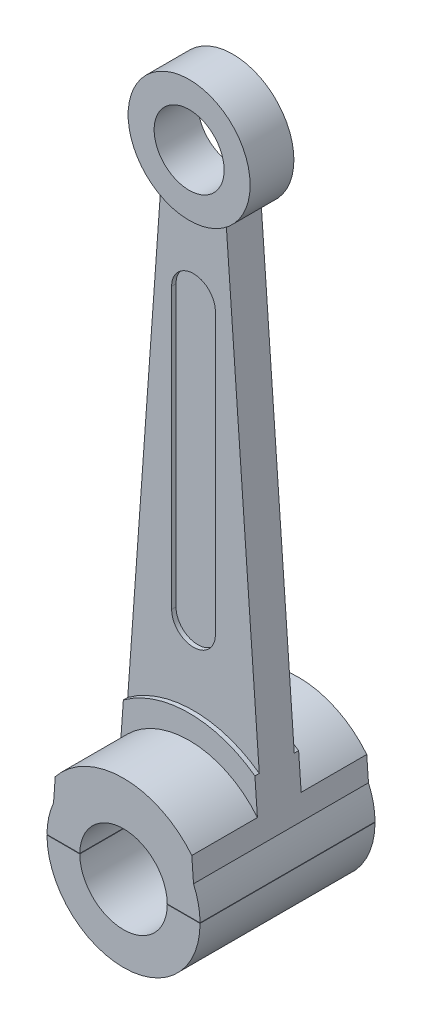
SolidWorks part; units mm, degrees
ref_plane "Front Plane" through (0, 0, 0) normal (0, 0, 1) x (1, 0, 0)
ref_plane "Top Plane" through (0, 0, 0) normal (0, 1, 0) x (1, 0, 0)
ref_plane "Right Plane" through (0, 0, 0) normal (1, 0, 0) x (0, 0, -1)
sketch "Sketch2" plane through (0, 0, 0) normal (0, 0, 1) x (1, 0, 0)
  line L0 (-2.989, 6.37) -> (-3.889, -4.2127)
  line L1 (-2.239, 7.5462) -> (-2.239, -6.1438) construction
  line L2 (-1.489, 6.37) -> (-0.589, -4.2127)
  line L3 (-2.739, 4.5462) -> (-2.739, -1.8525)
  line L4 (-1.739, 4.5462) -> (-1.739, -1.8525)
  circle A0 centre (-2.239, 7.5462) radius 1.395
  circle A1 centre (-2.239, 7.5462) radius 0.8
  circle A2 centre (-2.239, -6.1438) radius 2.54
  circle A3 centre (-2.239, -6.1438) radius 1
  arc A4 (-1.739, 4.5462) -> (-2.739, 4.5462) centre (-2.239, 4.5462) ccw
  arc A5 (-2.739, -1.8525) -> (-1.739, -1.8525) centre (-2.239, -1.8525) ccw
  dimension "D1" = 5.08
  dimension "D2" = 2
  dimension "D3" = 2.79
  dimension "D4" = 1.6
  dimension "D5" = 13.69
  dimension "D6" = 1
  dimension "D7" = 1
  dimension "D8" = 1.5
  dimension "D9" = 3
  dimension "D10" = 3.3
extrude "Boss-Extrude1" add sketch "Sketch2" along normal mid plane 1 contours A1 A0 | A2 A3 region at (-2.8907, 8.7348, 0) region at (-2.239, -3.6757, 0)
extrude "Boss-Extrude2" add sketch "Sketch2<4>" along normal mid plane 0.8 contours L1 A0 L0 A2 A5 L3 A4 | A0 L1 A4 L4 A5 A2 L2 region at (-3.0368, 0.2996, 0) region at (-1.4411, 0.2996, 0)
sketch "Sketch2<4>" plane through (0, 0, 0) normal (0, 0, 1) x (1, 0, 0) same geometry as "Sketch2"
extrude "Boss-Extrude3" add sketch "Sketch2<5>" along normal mid plane 0.6 contours L1 A4 L3 A5 | A4 L1 A5 L4 region at (-1.9931, 1.3469, 0) region at (-2.4848, 1.3469, 0)
sketch "Sketch2<5>" plane through (0, 0, 0) normal (0, 0, 1) x (1, 0, 0) same geometry as "Sketch2"
sketch "Sketch3" plane through (0, 0, 0.5) normal (0, 0, 1) x (1, 0, 0)
  circle A0 centre (-2.239, -6.1438) radius 1
  circle A1 centre (-2.239, -6.1438) radius 2
  dimension "D1" = 4
  dimension "D2" = 2
extrude "Boss-Extrude4" add sketch "Sketch3" along normal blind 1.5 and the other way blind 2.5
sketch "Sketch4" plane through (0, 0, 2) normal (0, 0, 1) x (1, 0, 0)
  line L0 (-5.2042, -4.2844) -> (-2.989, 6.37)
  line L1 (-1.489, 6.37) -> (0.7263, -4.2844)
  line L2 (-1.489, 6.37) -> (-0.589, -4.2127) construction
  line L3 (-3.839, -5.4349) -> (-2.989, 6.37)
  line L4 (-0.639, -5.4349) -> (-1.489, 6.37)
  arc A0 (-3.839, -5.4349) -> (-0.639, -5.4349) centre (-2.239, -6.1438) ccw
  arc A1 (-5.2042, -4.2844) -> (0.7263, -4.2844) centre (-2.239, -6.1438) ccw
  dimension "D2" = 1.75
  dimension "D3" = 3.5
  dimension "D1" = 3.2
extrude "Cut-Extrude1" cut sketch "Sketch4" against normal mid plane 31.5
sketch "Sketch5" plane through (0, 0, 2) normal (0, 0, 1) x (1, 0, 0)
  line L0 (-2.239, -6.1438) -> (0.2971, -6.1438) construction
  line L2 (-0.369, -6.1438) -> (-5.0568, -6.1438)
  line L3 (-0.369, -6.1438) -> (-0.369, -6.1338)
  line L4 (-0.369, -6.1338) -> (-5.0568, -6.1338)
  line L5 (-5.0568, -6.1438) -> (-5.0568, -6.1338)
  dimension "D1" = 0.01
extrude "Cut-Extrude2" cut sketch "Sketch5" against normal mid plane 31.5
